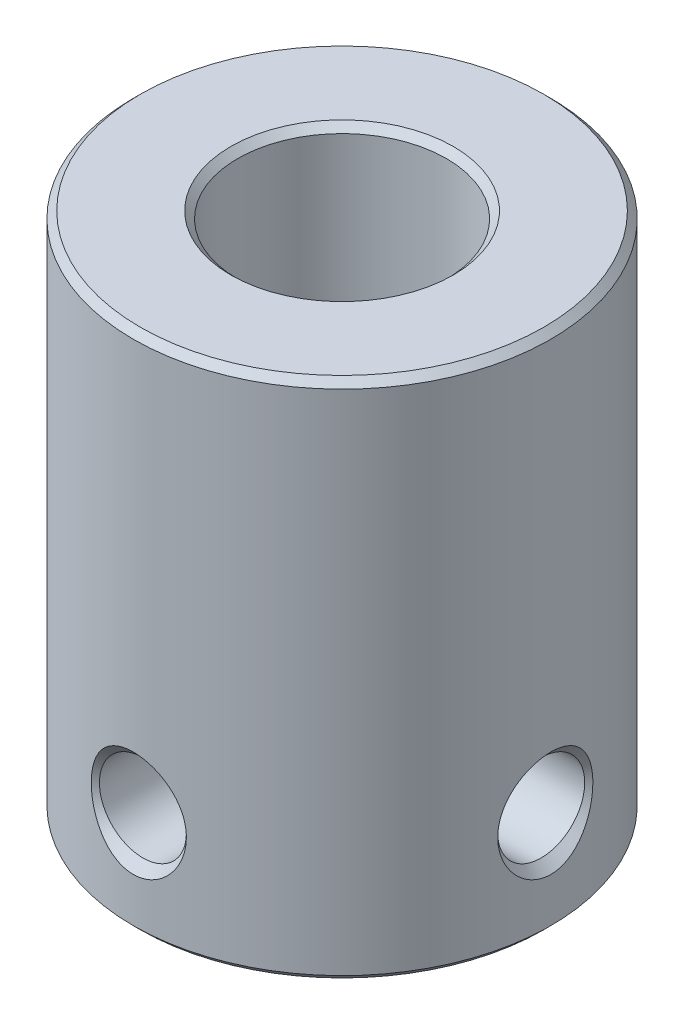
SolidWorks part; units mm, degrees
material "6061 Alloy"
ref_plane "Front Plane" through (0, 0, 0) normal (0, 0, 1) x (1, 0, 0)
ref_plane "Top Plane" through (0, 0, 0) normal (0, 1, 0) x (1, 0, 0)
ref_plane "Right Plane" through (0, 0, 0) normal (1, 0, 0) x (0, 0, -1)
sketch "ProfileS" plane through (0, 0, 0) normal (0, 1, 0) x (1, 0, 0)
  circle A0 centre (0, 0) radius 3
  circle A1 centre (0, 0) radius 6
  dimension "BoreDia" = 6
  dimension "RefOuterDia" = 12
  dimension "DiaControl" = 3
extrude "Profile" add sketch "ProfileS" along normal mid plane 15
ref_plane "SetScrewPlane" through (0, 0, 6) normal (0, 0, 1) x (1, 0, 0)
hole_wizard "M3x0.5 Tapped Hole1" positions "Sketch1" profile "Sketch2" tap size "M3x0.5" standard "ANSI Metric" end condition up to next
sketch "Sketch1" plane through (0, 0, 6) normal (0, 0, 1) x (1, 0, 0)
  line L0 (0, -7.5) -> (0, -4.5) construction
  line L1 (-6, -7.5) -> (6, -7.5) construction
  point P0 (0, -4.5)
  dimension "D1" = 3
sketch "Sketch2" plane through (0, -4.5, 6) normal (1, 0, 0) x (0, -1, 0)
  line L0 (0, 0) -> (0, 12)
  line L1 (0, 12) -> (1.25, 12)
  line L2 (1.25, 12) -> (1.25, 0.275)
  line L3 (1.25, 0.275) -> (1.525, 0)
  line L5 (1.525, 0) -> (0, 0)
  line L6 (-1.25, 0.275) -> (-1.525, 0) construction
  line L11 (0, -6.35) -> (0, 107.95) construction
  dimension "Thru Tap Drill Dia." = 2.5
  dimension "Thru Tap Drill Depth" = 12
  dimension "Near C'Sink Dia." = 3.05
  dimension "Near C'Sink Angle" = 90
cosmetic thread "Hole Thread1" parameters "D2"=3
pattern_circular "CirPattern1" count 2 over 90 about axis through (0, 7.5, 0) along (0, -1, 0) of "M3x0.5 Tapped Hole1" reverse direction yes
chamfer "OuterC" distance 0.2 angle 45 2 edges at (0, 7.5, 6) (0, -7.5, 6)
chamfer "InnerC" distance 0.2 angle 45 2 edges at (0, 7.5, 3) (0, -7.5, 3)
